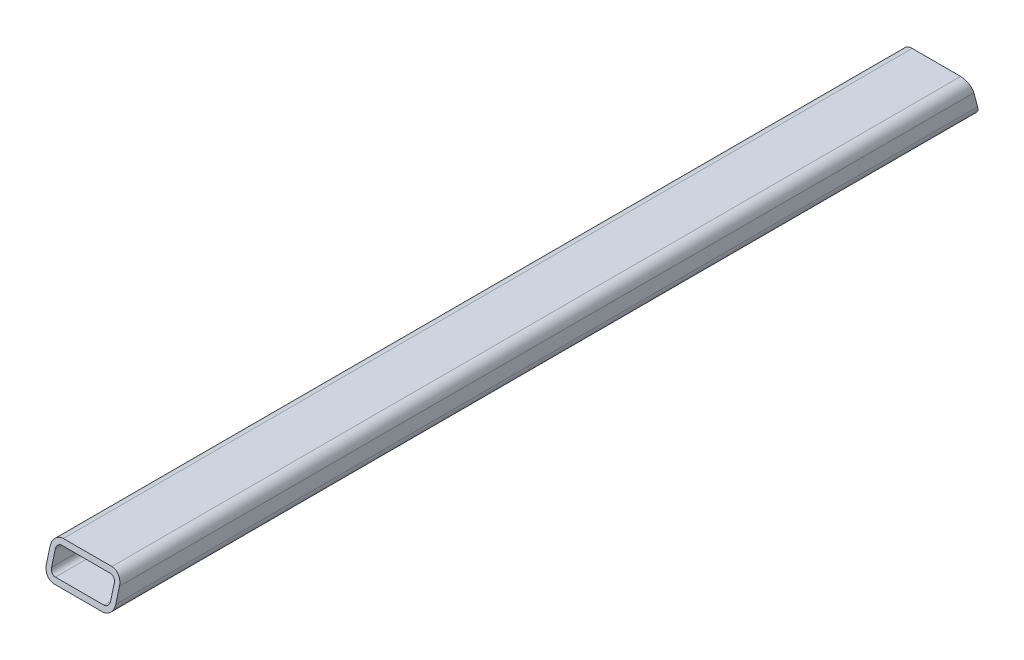
SolidWorks part; units mm, degrees
material "Ст 3 ГОСТ 380-88"
ref_plane "Спереди" through (0, 0, 0) normal (0, 0, 1) x (1, 0, 0)
ref_plane "Сверху" through (0, 0, 0) normal (0, 1, 0) x (1, 0, 0)
ref_plane "Справа" through (0, 0, 0) normal (1, 0, 0) x (0, 0, -1)
sketch "Эскиз1" plane through (0, 0, 0) normal (0, 0, 1) x (1, 0, 0)
  line L1 (-14, 10) -> (14, 10)
  line L2 (-20, 4) -> (-20, -4)
  line L3 (-14, -10) -> (14, -10)
  line L4 (20, 4) -> (20, -4)
  line L5 (-20, 10) -> (20, -10) construction
  line L6 (-20, -10) -> (20, 10) construction
  arc A0 (14, -10) -> (20, -4) centre (14, -4) ccw
  arc A1 (-14, 10) -> (-20, 4) centre (-14, 4) ccw
  arc A2 (-20, -4) -> (-14, -10) centre (-14, -4) ccw
  arc A3 (14, 10) -> (20, 4) centre (14, 4) cw
  point P0 (0, 0)
  dimension "D3" = 6
  dimension "D4" = 6
  dimension "D1" = 20
  dimension "D2" = 40
extrude "Бобышка-Вытянуть1" add sketch "Эскиз1" along normal blind 250 and the other way blind 250
shell "Оболочка1" thickness 3 removed face at (0, 0, -250) removed face at (0, 0, 250)
chamfer "Фаска1" distance 20 angle 15 2 edges at (0, 10, -250) (0, 10, 250) tangent propagation no first distance on face at (0, 0, -250) first distance on face at (0, 0, 250)
